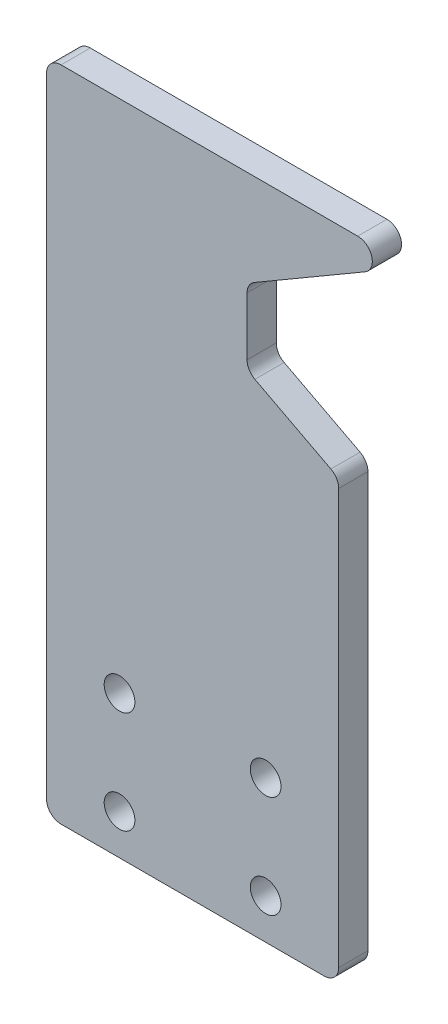
SolidWorks part; units mm, degrees
material "Thornel Mat VMA"
ref_plane "前视基准面" through (0, 0, 0) normal (0, 0, 1) x (1, 0, 0)
ref_plane "上视基准面" through (0, 0, 0) normal (0, 1, 0) x (1, 0, 0)
ref_plane "右视基准面" through (0, 0, 0) normal (1, 0, 0) x (0, 0, -1)
other "Configuration Table"
sketch "草图1" plane through (0, 0, 0) normal (0, 0, 1) x (1, 0, 0)
  line L0 (-20, 60) -> (-20, 30)
  line L2 (-20, 30) -> (-20, -30)
  line L3 (-20, -30) -> (20, -30)
  line L4 (20, 30) -> (20, -30)
  line L5 (-20, 30) -> (20, -30) construction
  line L6 (-20, -30) -> (20, 30) construction
  line L7 (-20, 30) -> (-5.963, 30)
  line L8 (-20, 60) -> (22.6016, 60)
  line L10 (23.6093, 56.2724) -> (7.4529, 46.8486)
  line L11 (7.4529, 46.8486) -> (7.4529, 36.5504)
  line L12 (7.4529, 36.5504) -> (20, 30)
  arc A0 (22.6016, 60) -> (23.6093, 56.2724) centre (22.6016, 58) cw
  point P0 (0, 0)
  point P19 (30, 60)
  dimension "D7" = 2
  dimension "D1" = 40
  dimension "D2" = 60
  dimension "D3" = 90
  dimension "D4" = 30
  dimension "D5" = 50
extrude "凸台-拉伸1" add sketch "草图1" along normal blind 4 contours L4 L2 L3 region at (-0.7991, 13.5353, 0)
sketch "草图2" plane through (0, 0, 4) normal (0, 0, 1) x (1, 0, 0)
  line L1 (-20, -30) -> (20, -30) construction
  line L2 (0, -30) -> (0, -4.5877) construction
  circle A0 centre (-10, -24.5) radius 2.1
  circle A1 centre (-10, -10.5) radius 2.1
  circle A2 centre (10, -10.5) radius 2.1
  circle A3 centre (10, -24.5) radius 2.1
  dimension "D2" = 5.5
  dimension "D1" = 4.2
  dimension "D3" = 20
  dimension "D5" = 14
extrude "切除-拉伸1" cut sketch "草图2" against normal up to next contours A1 | A0 | A2 | A3 region at (-10, -24.5, 4) region at (-10, -10.5, 4) region at (10, -10.5, 4) region at (10, -24.5, 4)
sketch "草图3" plane through (0, 0, 4) normal (0, 0, 1) x (1, 0, 0)
  line L1 (20, 30) -> (20, -30) construction
  circle A2 centre (-0.5, 14.8805) radius 10.5 construction
  circle A3 centre (10, 14.8805) radius 2.25
  circle A10 centre (-5.75, 5.7872) radius 2.25
  circle A11 centre (-5.75, 23.9738) radius 2.25
  point P13 (-0.5, 14.8805)
  dimension "D1" = 21
  dimension "D2" = 4.5
  dimension "D3" = 3
  dimension "D4" = 10
fillet "圆角1" radius 2 6 edges at (-20, 60, 2) (20, 30, 2) (20, -30, 2) (-20, -30, 2) (7.4529, 46.8486, 2) (7.4529, 36.5504, 2)
